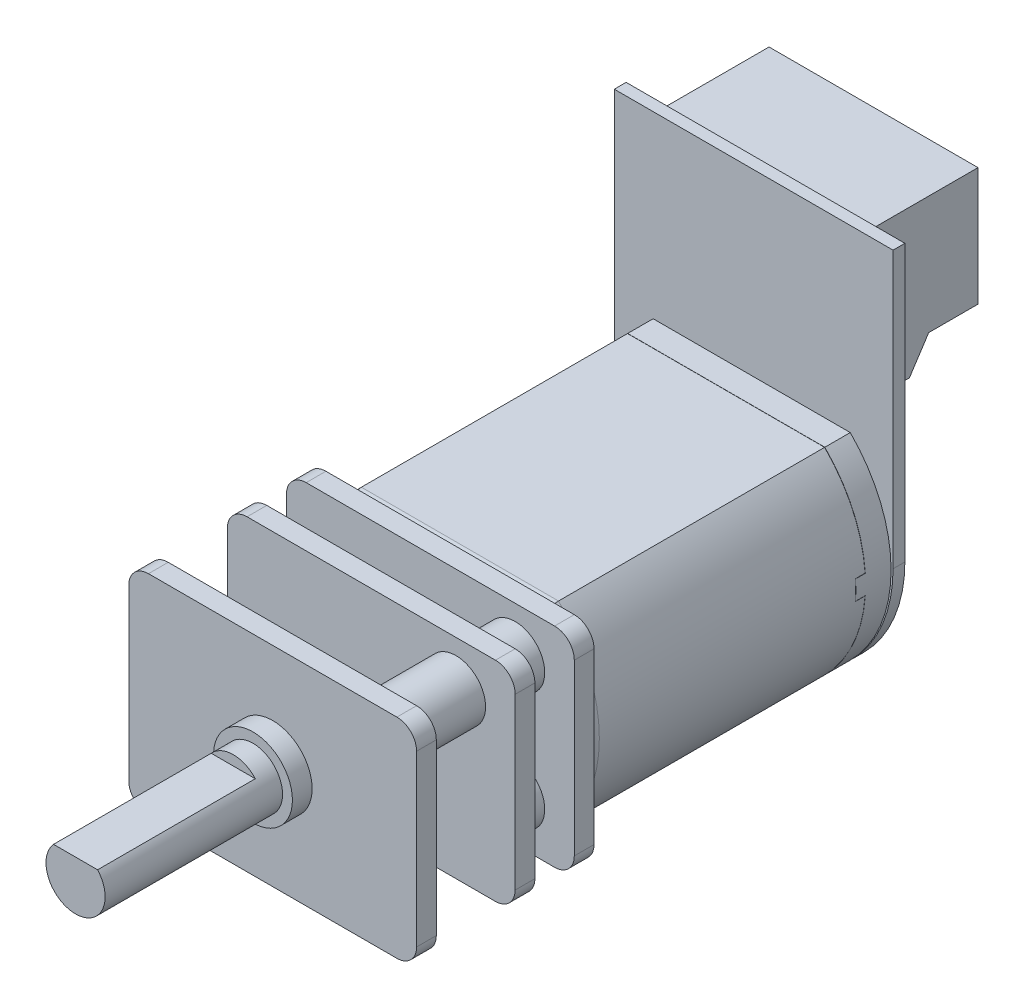
SolidWorks part; units mm, degrees
ref_plane "Front Plane" through (0, 0, 0) normal (0, 0, 1) x (1, 0, 0)
ref_plane "Top Plane" through (0, 0, 0) normal (0, 1, 0) x (1, 0, 0)
ref_plane "Right Plane" through (0, 0, 0) normal (1, 0, 0) x (0, 0, -1)
sketch "Sketch1" plane through (0, 0, 0) normal (0, 0, 1) x (1, 0, 0)
  line L1 (-5, 5) -> (5, 5)
  line L3 (-5, -5) -> (5, -5)
  line L5 (-5, 5) -> (5, -5) construction
  line L6 (-5, -5) -> (5, 5) construction
  arc A0 (-5, 5) -> (-5, -5) centre (0, 0) ccw
  arc A1 (5, -5) -> (5, 5) centre (0, 0) ccw
  dimension "D2" = 10
  dimension "D1" = 10
extrude "Boss-Extrude1" add sketch "Sketch1" along normal mid plane 14
fillet "Fillet1" radius 0.5 4 edges at (-7.0711, 0, 7) (0, -5, 7) (7.0711, 0, 7) (0, 5, 7)
sketch "Sketch2" plane through (0, 0, 0) normal (1, 0, 0) x (0, 0, -1)
  line L0 (7, -5) -> (7, 5) construction
  line L1 (6.5, 0.5) -> (7.5, 0.5)
  line L2 (6.5, 0.5) -> (6.5, -0.5)
  line L3 (6.5, -0.5) -> (7.5, -0.5)
  line L4 (7.5, 0.5) -> (7.5, -0.5)
  line L5 (6.5, 0.5) -> (7.5, -0.5) construction
  line L6 (6.5, -0.5) -> (7.5, 0.5) construction
  point P0 (7, 0)
  dimension "D1" = 1
  dimension "D2" = 1
extrude "Cut-Extrude1" cut sketch "Sketch2" against normal mid plane 16
sketch "Sketch3" plane through (0, 0, 0) normal (1, 0, 0) x (0, 0, -1)
  line L0 (7, 5) -> (7, 0.5) construction
  line L1 (7, 0.5) -> (6.5, 0.5) construction
  line L2 (6.5, 0.5) -> (6.5, -0.5) construction
  line L3 (6.5, -0.5) -> (7, -0.5) construction
  line L4 (7, -0.5) -> (7, -5) construction
  line L5 (7.01, -5) -> (8.3, -5)
  line L6 (8.3, -5) -> (8.3, 5)
  line L7 (8.3, 5) -> (7.01, 5)
  line L8 (7.01, 5) -> (7.01, 0.49)
  line L9 (7.01, 0.49) -> (6.51, 0.49)
  line L10 (6.51, 0.49) -> (6.51, -0.49)
  line L11 (6.51, -0.49) -> (7.01, -0.49)
  line L12 (7.01, -0.49) -> (7.01, -5)
  dimension "D1" = 1.3
  dimension "D2" = 0.01
extrude "Boss-Extrude2" add sketch "Sketch3" along normal up to surface and the other way up to surface up to face at (6.3894, 0, -3.5) other way up to face at (-6.3894, 0, -3.5)
sketch "Sketch4" plane through (0, 0, -8.3) normal (0, 0, -1) x (-1, 0, 0)
  line L1 (-0.5, 0.5) -> (0.5, 0.5)
  line L2 (-0.5, 0.5) -> (-0.5, -0.5)
  line L3 (-0.5, -0.5) -> (0.5, -0.5)
  line L4 (0.5, 0.5) -> (0.5, -0.5)
  line L5 (-0.5, 0.5) -> (0.5, -0.5) construction
  line L6 (-0.5, -0.5) -> (0.5, 0.5) construction
  point P0 (0, 0)
  dimension "D1" = 1
  dimension "D2" = 1
extrude "Boss-Extrude3" add sketch "Sketch4" along normal blind 1
ref_plane "Plane1" through (0, 0, -8.4) normal (0, 0, -1) x (-1, 0, 0)
sketch "Sketch5" plane through (0, 0, -8.4) normal (0, 0, -1) x (-1, 0, 0)
  line L0 (-5, -5) -> (5, -5)
  line L1 (-7.0711, 0) -> (7.0711, 0) construction
  line L2 (-7.0711, 0) -> (-7.0711, 14)
  line L3 (-7.0711, 14) -> (7.0711, 14)
  line L4 (7.0711, 14) -> (7.0711, 0)
  arc A0 (-7.0711, 0) -> (-5, -5) centre (0, 0) ccw
  arc A1 (5, -5) -> (7.0711, 0) centre (0, 0) ccw
  dimension "D1" = 19
extrude "Boss-Extrude4" add sketch "Sketch5" along normal blind 0.6
sketch "Sketch6" plane through (0, 0, 0) normal (1, 0, 0) x (0, 0, -1)
  line L0 (9, 13.7) -> (14.48, 13.7)
  line L1 (9, 14) -> (9, 0) construction
  line L2 (14.48, 13.7) -> (14.48, 7.7)
  line L3 (14.48, 7.7) -> (11.98, 7.7)
  line L4 (11.98, 7.7) -> (11, 6.2)
  line L5 (11, 6.2) -> (9, 6.2)
  line L6 (9, 6.2) -> (9, 13.7)
  line L7 (9, 14) -> (8.4, 14) construction
  dimension "D1" = 5.48
  dimension "D2" = 6
  dimension "D3" = 0.3
  dimension "D4" = 1.5
  dimension "D5" = 2
  dimension "D6" = 2.5
extrude "Boss-Extrude5" add sketch "Sketch6" along normal mid plane 10.6
shell "Shell1" thickness 0.7 removed face at (0, 10.7, -14.48)
sketch "Sketch7" plane through (0, 0, 7) normal (0, 0, 1) x (1, 0, 0)
  line L0 (-5, 5) -> (5, 5) construction
  line L1 (-6.3, 5.3) -> (6.3, 5.3)
  line L2 (-7.3, 4.3) -> (-7.3, -4.3)
  line L3 (-6.3, -5.3) -> (6.3, -5.3)
  line L4 (7.3, 4.3) -> (7.3, -4.3)
  line L5 (-7.3, 5.3) -> (7.3, -5.3) construction
  line L6 (-7.3, -5.3) -> (7.3, 5.3) construction
  arc A0 (-5, 5) -> (-5, -5) centre (0, 0) ccw construction
  arc A1 (-7.3, -4.3) -> (-6.3, -5.3) centre (-6.3, -4.3) ccw
  arc A2 (6.3, -5.3) -> (7.3, -4.3) centre (6.3, -4.3) ccw
  arc A3 (6.3, 5.3) -> (7.3, 4.3) centre (6.3, 4.3) cw
  arc A4 (-6.3, 5.3) -> (-7.3, 4.3) centre (-6.3, 4.3) ccw
  point P0 (0, 0)
  dimension "D3" = 1
  dimension "D1" = 0.3
  dimension "D2" = 7.3
extrude "Boss-Extrude6" add sketch "Sketch7" along normal blind 1
sketch "Sketch8" plane through (0, 0, 8) normal (0, 0, 1) x (1, 0, 0)
  line L0 (4.3, -5.3) -> (4.3, 5.3) construction
  line L1 (-6.3, -5.3) -> (6.3, -5.3) construction
  line L2 (6.3, 5.3) -> (-6.3, 5.3) construction
  line L3 (7.3, -4.3) -> (7.3, 4.3) construction
  line L4 (-7.3, 4.3) -> (-7.3, -4.3) construction
  circle A0 centre (4.3, 3) radius 1.5
  circle A1 centre (4.3, -3) radius 1.5
  circle A2 centre (-4.3, -3) radius 1.5
  dimension "D2" = 3
  dimension "D6" = 3
  dimension "D1" = 3
  dimension "D3" = 2.3
  dimension "D4" = 2.3
  dimension "D5" = 3
  dimension "D7" = 2.3
extrude "Boss-Extrude7" add sketch "Sketch8" along normal blind 2
sketch "Sketch10" plane through (0, 0, 10) normal (0, 0, 1) x (1, 0, 0)
  line L30 (7.3, -4.3) -> (7.3, 4.3)
  line L31 (-6.3, -5.3) -> (6.3, -5.3)
  line L32 (-7.3, 4.3) -> (-7.3, -4.3)
  line L33 (6.3, 5.3) -> (-6.3, 5.3)
  line L34 (7.3, -4.3) -> (7.3, 4.3)
  line L35 (-6.3, -5.3) -> (6.3, -5.3)
  line L36 (-7.3, 4.3) -> (-7.3, -4.3)
  line L37 (6.3, 5.3) -> (-6.3, 5.3)
  arc A15 (-6.3, 5.3) -> (-7.3, 4.3) centre (-6.3, 4.3) ccw
  arc A16 (-7.3, -4.3) -> (-6.3, -5.3) centre (-6.3, -4.3) ccw
  arc A17 (6.3, -5.3) -> (7.3, -4.3) centre (6.3, -4.3) ccw
  arc A18 (7.3, 4.3) -> (6.3, 5.3) centre (6.3, 4.3) ccw
  arc A19 (-6.3, 5.3) -> (-7.3, 4.3) centre (-6.3, 4.3) ccw
  arc A20 (-7.3, -4.3) -> (-6.3, -5.3) centre (-6.3, -4.3) ccw
  arc A21 (6.3, -5.3) -> (7.3, -4.3) centre (6.3, -4.3) ccw
  arc A22 (7.3, 4.3) -> (6.3, 5.3) centre (6.3, 4.3) ccw
  dimension "D1" = 0
extrude "Boss-Extrude8" add sketch "Sketch10" along normal blind 1
sketch "Sketch12" plane through (0, 0, 11) normal (0, 0, 1) x (1, 0, 0)
  circle A5 centre (-4.3, -3) radius 1.5
  circle A6 centre (-4.3, -3) radius 1.5
  circle A8 centre (4.3, 3) radius 1.5
  circle A9 centre (4.3, 3) radius 1.5
  dimension "D1" = 0
  dimension "D2" = 0
extrude "Boss-Extrude9" add sketch "Sketch12" along normal blind 4
sketch "Sketch13" plane through (0, 0, 15) normal (0, 0, 1) x (1, 0, 0)
  line L8 (6.3, 5.3) -> (-6.3, 5.3)
  line L9 (-7.3, 4.3) -> (-7.3, -4.3)
  line L10 (-6.3, -5.3) -> (6.3, -5.3)
  line L11 (7.3, -4.3) -> (7.3, 4.3)
  line L12 (6.3, 5.3) -> (-6.3, 5.3)
  line L13 (-7.3, 4.3) -> (-7.3, -4.3)
  line L14 (-6.3, -5.3) -> (6.3, -5.3)
  line L15 (7.3, -4.3) -> (7.3, 4.3)
  arc A8 (7.3, 4.3) -> (6.3, 5.3) centre (6.3, 4.3) ccw
  arc A9 (-6.3, 5.3) -> (-7.3, 4.3) centre (-6.3, 4.3) ccw
  arc A10 (-7.3, -4.3) -> (-6.3, -5.3) centre (-6.3, -4.3) ccw
  arc A11 (6.3, -5.3) -> (7.3, -4.3) centre (6.3, -4.3) ccw
  arc A12 (7.3, 4.3) -> (6.3, 5.3) centre (6.3, 4.3) ccw
  arc A13 (-6.3, 5.3) -> (-7.3, 4.3) centre (-6.3, 4.3) ccw
  arc A14 (-7.3, -4.3) -> (-6.3, -5.3) centre (-6.3, -4.3) ccw
  arc A15 (6.3, -5.3) -> (7.3, -4.3) centre (6.3, -4.3) ccw
  dimension "D1" = 0
extrude "Boss-Extrude10" add sketch "Sketch13" along normal blind 1
sketch "Sketch14" plane through (0, 0, 16) normal (0, 0, 1) x (1, 0, 0)
  circle A0 centre (0, 0) radius 1.5
  dimension "D1" = 3
extrude "Cut-Extrude2" cut sketch "Sketch14" against normal blind 1
sketch "Sketch15" plane through (0, 0, 16) normal (0, 0, 1) x (1, 0, 0)
  circle A1 centre (0, 0) radius 2
  circle A2 centre (0, 0) radius 1.5
  circle A3 centre (0, 0) radius 1.5
  dimension "D2" = 4
  dimension "D1" = 0
extrude "Boss-Extrude11" add sketch "Sketch15" along normal blind 1
sketch "Sketch16" plane through (0, 0, 15) normal (0, 0, -1) x (-1, 0, 0)
  circle A2 centre (0, 0) radius 1.5
  circle A3 centre (0, 0) radius 1.5
  dimension "D1" = 0
extrude "Boss-Extrude12" add sketch "Sketch16" against normal blind 11
sketch "Sketch17" plane through (0, 0, 26) normal (0, 0, 1) x (1, 0, 0)
  line L0 (0, 1.5) -> (0, -1.5) construction
  line L1 (-2.393, 1) -> (2.3621, 1)
  line L2 (-2.393, 1) -> (-2.393, 3)
  line L3 (-2.393, 3) -> (2.3621, 3)
  line L4 (2.3621, 1) -> (2.3621, 3)
  circle A0 centre (0, 0) radius 1.5 construction
  circle A1 centre (0, 0) radius 1.5 construction
  dimension "D1" = 2.5
extrude "Cut-Extrude3" cut sketch "Sketch17" against normal blind 8
